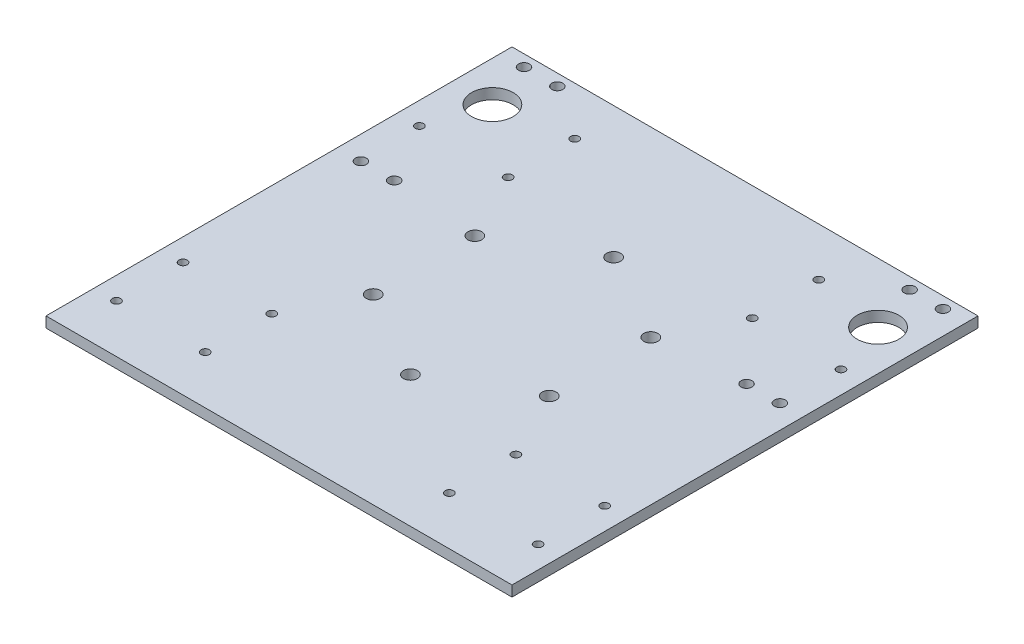
SolidWorks part; units mm, degrees
ref_plane "Front Plane" through (0, 0, 0) normal (0, 0, 1) x (1, 0, 0)
ref_plane "Top Plane" through (0, 0, 0) normal (0, 1, 0) x (1, 0, 0)
ref_plane "Right Plane" through (0, 0, 0) normal (1, 0, 0) x (0, 0, -1)
sketch "Sketch1" plane through (0, 0, 0) normal (0, 1, 0) x (1, 0, 0)
  line L1 (-70, -70) -> (70, -70)
  line L2 (-70, -70) -> (-70, 70)
  line L3 (-70, 70) -> (70, 70)
  line L4 (70, -70) -> (70, 70)
  line L5 (-70, -70) -> (70, 70) construction
  line L6 (-70, 70) -> (70, -70) construction
  point P0 (0, 0)
  dimension "D1" = 140
  dimension "D2" = 140
extrude "Boss-Extrude1" add sketch "Sketch1" along normal blind 3.175
sketch "Sketch2" plane through (0, 3.175, 0) normal (0, 1, 0) x (1, 0, 0)
  line L0 (-45, 30.5) -> (-30, 30.5) construction
  line L1 (-45, -30.5) -> (45, -30.5) construction
  line L2 (-45, -30.5) -> (-45, 30.5) construction
  line L3 (-45, 30.5) -> (45, 30.5) construction
  line L4 (45, -30.5) -> (45, 30.5) construction
  line L5 (-45, -30.5) -> (45, 30.5) construction
  line L6 (-45, 30.5) -> (45, -30.5) construction
  line L7 (-30, 30.5) -> (-30, 60.5) construction
  line L8 (-70, 70) -> (-70, -70) construction
  line L9 (-30, 60.5) -> (-70, 60.5) construction
  line L10 (-30, 60.5) -> (-30, 30.5) construction
  line L11 (-30, 30.5) -> (-70, 30.5) construction
  line L12 (-70, 60.5) -> (-70, 30.5) construction
  line L13 (-30, 60.5) -> (-70, 30.5) construction
  line L14 (-30, 30.5) -> (-70, 60.5) construction
  line L15 (-51.4643, -23.9643) -> (-51.4643, 60.5) construction
  line L16 (-70, 45.5) -> (-30, 45.5) construction
  line L17 (-50, 60.5) -> (-50, 30.5) construction
  line L18 (-57.9286, 52.0357) -> (-57.9286, 62.0357) construction
  line L19 (-62.9286, 66.5357) -> (-52.9286, 66.5357) construction
  line L20 (-67.9286, 62.0357) -> (-47.9286, 62.0357) construction
  line L21 (-67.9286, 62.0357) -> (-67.9286, 22.0357) construction
  line L22 (-67.9286, 22.0357) -> (-47.9286, 22.0357) construction
  line L23 (-47.9286, 62.0357) -> (-47.9286, 22.0357) construction
  line L24 (-67.9286, 62.0357) -> (-47.9286, 22.0357) construction
  line L25 (-67.9286, 22.0357) -> (-47.9286, 62.0357) construction
  line L26 (-67.9286, 17.5357) -> (-47.9286, 17.5357) construction
  line L27 (-67.9286, 17.5357) -> (-67.9286, 66.5357) construction
  line L28 (-67.9286, 66.5357) -> (-47.9286, 66.5357) construction
  line L29 (-47.9286, 17.5357) -> (-47.9286, 66.5357) construction
  line L30 (-67.9286, 17.5357) -> (-47.9286, 66.5357) construction
  line L31 (-67.9286, 66.5357) -> (-47.9286, 17.5357) construction
  line L32 (-67.9286, 14.0357) -> (-47.9286, 14.0357) construction
  line L33 (-67.9286, 14.0357) -> (-67.9286, 70.0357) construction
  line L34 (-67.9286, 70.0357) -> (-47.9286, 70.0357) construction
  line L35 (-47.9286, 14.0357) -> (-47.9286, 70.0357) construction
  line L36 (-67.9286, 14.0357) -> (-47.9286, 70.0357) construction
  line L37 (-67.9286, 70.0357) -> (-47.9286, 14.0357) construction
  line L38 (-67.9286, 42.0357) -> (-47.9286, 42.0357) construction
  line L39 (0, -1.7463) -> (0, 1.7463) construction
  line L40 (-45, 30.5) -> (-45, 45.5) construction
  line L41 (-1.7463, 0) -> (1.7463, 0) construction
  line L42 (-67.9286, 52.0357) -> (-30, 52.0357) construction
  circle A0 centre (-45, 0) radius 6.4643 construction
  circle A1 centre (-57.9286, 52.0357) radius 6.4643 construction
  circle A2 centre (-57.9286, 52.0357) radius 6.25
  circle A8 centre (-57.9286, 52.0357) radius 2.45 construction
  circle A9 centre (-62.9286, 66.5357) radius 1.65
  circle A10 centre (-52.9286, 66.5357) radius 1.65
  circle A11 centre (-52.9286, 17.5357) radius 1.65
  circle A12 centre (-62.9286, 17.5357) radius 1.65
  circle A13 centre (52.9286, 17.5357) radius 1.65
  circle A14 centre (62.9286, 17.5357) radius 1.65
  circle A15 centre (57.9286, 52.0357) radius 6.25
  circle A16 centre (52.9286, 66.5357) radius 1.65
  circle A17 centre (62.9286, 66.5357) radius 1.65
  circle A18 centre (-36.6667, 55.5) radius 1.25
  circle A19 centre (-36.6667, 35.5) radius 1.25
  circle A20 centre (-63.3333, 35.5) radius 1.25
  circle A21 centre (-63.3333, 55.5) radius 1.25 construction
  circle A22 centre (36.6667, 35.5) radius 1.25
  circle A23 centre (63.3333, 35.5) radius 1.25
  circle A24 centre (36.6667, 55.5) radius 1.25
  circle A25 centre (63.3333, 55.5) radius 1.25 construction
  circle A26 centre (63.3333, -35.5) radius 1.25
  circle A27 centre (36.6667, -35.5) radius 1.25
  circle A28 centre (63.3333, -55.5) radius 1.25
  circle A29 centre (36.6667, -55.5) radius 1.25
  circle A30 centre (-36.6667, -35.5) radius 1.25
  circle A31 centre (-63.3333, -35.5) radius 1.25
  circle A32 centre (-36.6667, -55.5) radius 1.25
  circle A33 centre (-63.3333, -55.5) radius 1.25
  point P0 (0, 0)
  point P10 (-50, 45.5)
  point P25 (-57.9286, 42.0357)
  point P31 (-57.9286, 42.0357)
  point P32 (-57.9286, 62.0357)
  point P37 (-57.9286, 42.0357)
  point P44 (-57.9286, 66.5357)
  point P45 (-57.9286, 66.5357)
  dimension "D5" = 12.9286
  dimension "D6" = 12.9286
  dimension "D7" = 12.5
  dimension "D8" = 4.9
  dimension "D14" = 10
  dimension "D9" = 10
  dimension "D15" = 3.3
  dimension "D16" = 2.5
  dimension "D1" = 90
  dimension "D2" = 61
  dimension "D3" = 15
  dimension "D4" = 30
  dimension "D10" = 20
  dimension "D11" = 40
  dimension "D12" = 49
  dimension "D13" = 56
  dimension "D17" = 5
  dimension "D18" = 8.4643
sketch "Sketch4" plane through (0, 3.175, 0) normal (0, 1, 0) x (1, 0, 0)
  line L0 (0, 0) -> (0, 30.525) construction
  line L1 (0, 0) -> (26.4354, 15.2625) construction
  circle A0 centre (0, 0) radius 40 construction
  circle A1 centre (0, 0) radius 30.525 construction
  circle A2 centre (0, 30.525) radius 2.1
  circle A3 centre (26.4354, 15.2625) radius 2.1
  circle A4 centre (26.4354, -15.2625) radius 2.1
  circle A5 centre (0, -30.525) radius 2.1
  circle A6 centre (-26.4354, -15.2625) radius 2.1
  circle A7 centre (-26.4354, 15.2625) radius 2.1
  dimension "D1" = 80
  dimension "D2" = 61.05
  dimension "D3" = 4.2
  dimension "D5" = 60
  dimension "D4" = 6
extrude "Cut-Extrude1" cut sketch "Sketch2" against normal up to surface (3.175 mm away) contours A9 | A10 | A18 | A2 | A19 | A20 | A11 | A12 | A16 | A17 | A24 | A15 | A23 | A22 | A13 | A14 | A31 | A30 | A33 | A32 | A27 | A26 | A29 | A28 up to face at (0, 0, 0)
extrude "Cut-Extrude2" cut sketch "Sketch4" against normal up to surface (3.175 mm away) contours A7 | A2 | A3 | A6 | A4 | A5 up to face at (57.9286, 0, -58.2857)
